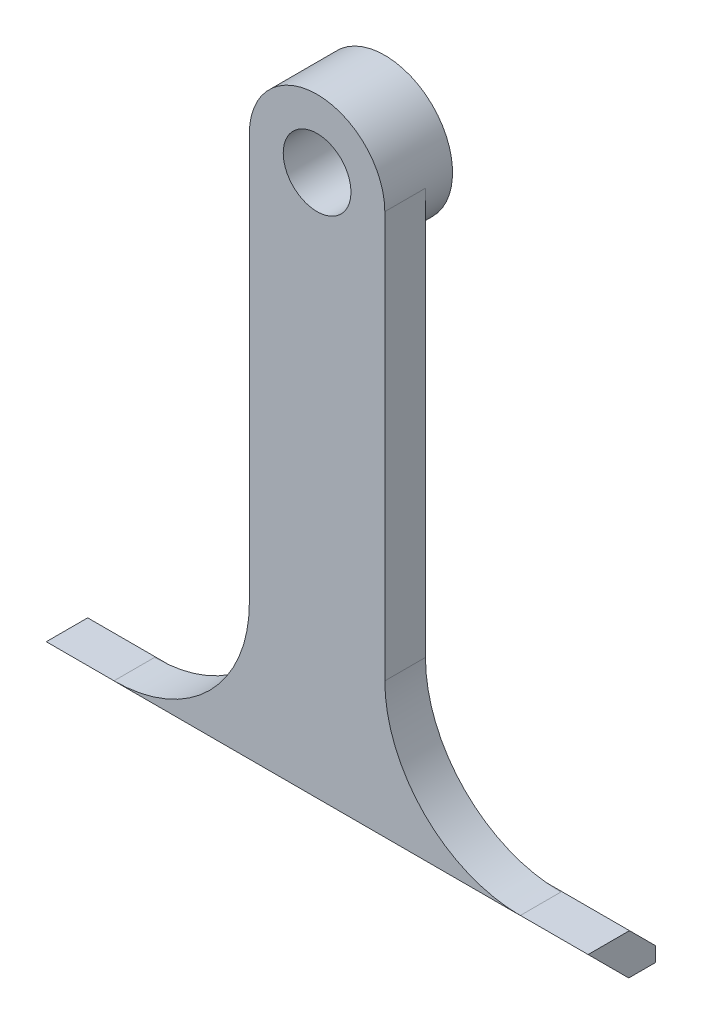
SolidWorks part; units mm, degrees
ref_plane "Front Plane" through (0, 0, 0) normal (0, 0, 1) x (1, 0, 0)
ref_plane "Top Plane" through (0, 0, 0) normal (0, 1, 0) x (1, 0, 0)
ref_plane "Right Plane" through (0, 0, 0) normal (1, 0, 0) x (0, 0, -1)
sketch "Sketch1" plane through (0, 0, 0) normal (0, 1, 0) x (1, 0, 0)
  line L1 (-50.8, 25.4) -> (50.8, 25.4)
  line L2 (-50.8, 25.4) -> (-50.8, 0)
  line L3 (-25.4, -25.4) -> (25.4, -25.4)
  line L4 (50.8, 25.4) -> (50.8, 0)
  line L5 (-50.8, 25.4) -> (50.8, -25.4) construction
  line L6 (-50.8, -25.4) -> (50.8, 25.4) construction
  arc A0 (25.4, -25.4) -> (50.8, 0) centre (25.4, 0) ccw
  arc A1 (-50.8, 0) -> (-25.4, -25.4) centre (-25.4, 0) ccw
  circle A3 centre (-25.4, 0) radius 6.35
  circle A4 centre (25.4, 0) radius 6.35
  point P0 (0, 0)
  point P12 (0, 0)
  dimension "D3" = 25.4
  dimension "D1" = 50.8
  dimension "D2" = 101.6
extrude "Boss-Extrude1" add sketch "Sketch1" along normal blind 7.62 contours L2 A1 L3 A0 L4 L1 | A3 | A4
sketch "Sketch4" plane through (0, 0, -25.4) normal (0, 0, -1) x (-1, 0, 0)
  line L0 (12.7, 109.22) -> (12.7, 7.62)
  line L1 (50.8, 7.62) -> (-50.8, 7.62) construction
  line L2 (-12.7, 109.22) -> (-12.7, 7.62)
  circle A0 centre (0, 109.22) radius 12.7
  circle A1 centre (0, 109.22) radius 6.35
  line M5 (50.8, 7.62) -> (-50.8, 7.62)
  dimension "D1" = 101.6
  dimension "D2" = 25.4
extrude "Boss-Extrude2" add sketch "Sketch4" against normal blind 7.62 from offset 5.08 contours A0 L2 L0 M5 | A0 A1 region at (0, 96.8792, -25.4) region at (0, 53.4766, -25.4) offset against normal yes
extrude "Boss-Extrude3" add sketch "Sketch4<3>" along normal blind 5.08 from offset 5.08 contours A0 A1 region at (0, 96.8792, -25.4) offset against normal yes
sketch "Sketch4<3>" plane through (0, 0, -25.4) normal (0, 0, -1) x (-1, 0, 0) same geometry as "Sketch4"
fillet "Fillet1" radius 25.4 2 edges at (-12.7, 7.62, -16.51) (12.7, 7.62, -16.51)
chamfer "Chamfer1" distance 4.92 angle 45 1 edges at (0, 7.62, -25.4)
sketch "Sketch8" plane through (50.8, 0, 0) normal (1, 0, 0) x (0, 0, -1)
  line L0 (12.7175, 7.62) -> (20.3375, 0)
  line L1 (20.48, 7.62) -> (0, 7.62) construction
  line L2 (25.4, 0) -> (0, 0) construction
  line L3 (12.7175, 7.62) -> (-26.5845, 7.62)
  line L4 (-26.5845, 7.62) -> (-26.5845, 0)
  line L5 (-26.5845, 0) -> (20.3375, 0)
extrude "Cut-Extrude1" cut sketch "Sketch8" against normal through all
